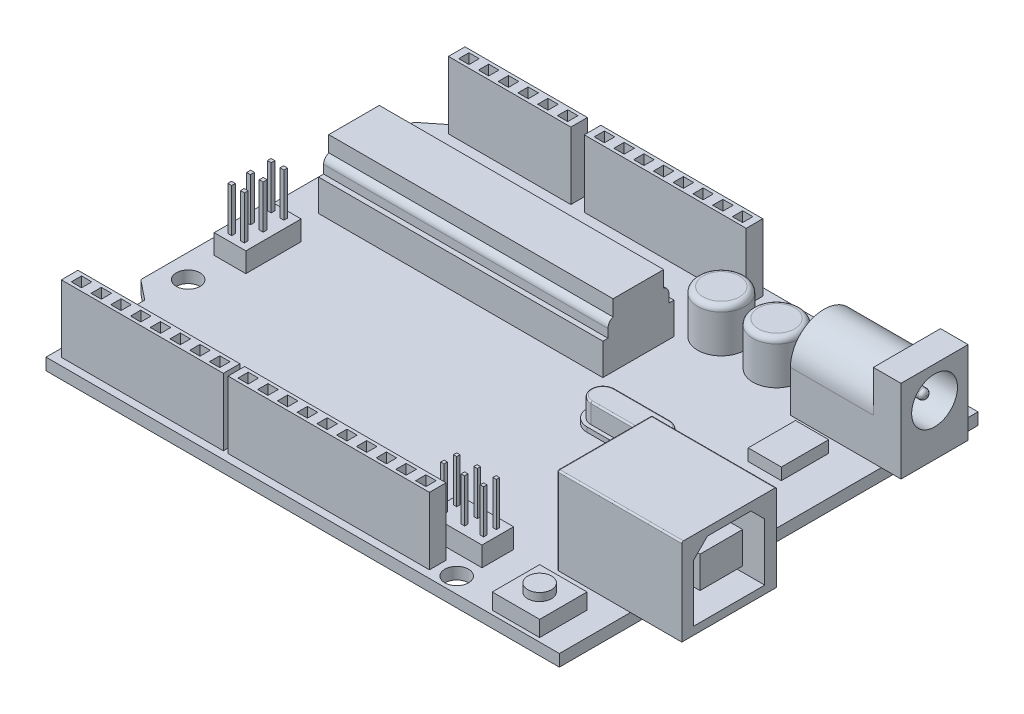
SolidWorks part; units mm, degrees
ref_plane "Front Plane" through (0, 0, 0) normal (0, 0, 1) x (1, 0, 0)
ref_plane "Top Plane" through (0, 0, 0) normal (0, 1, 0) x (1, 0, 0)
ref_plane "Right Plane" through (0, 0, 0) normal (1, 0, 0) x (0, 0, -1)
sketch "Sketch1" plane through (0, 0, 0) normal (0, 1, 0) x (1, 0, 0)
  line L0 (-32.5, -26.5) -> (-32.5, -14)
  line L1 (-32.5, 26.5) -> (32.5, 26.5)
  line L2 (-32.5, 26.5) -> (-32.5, -26.5) construction
  line L3 (-32.5, -26.5) -> (32.5, -26.5)
  line L4 (32.5, 26.5) -> (32.5, -26.5)
  line L5 (-32.5, 26.5) -> (32.5, -26.5) construction
  line L6 (-32.5, -26.5) -> (32.5, 26.5) construction
  line L7 (-32.5, 26.5) -> (-32.5, 24.5)
  line L8 (-32.5, 24.5) -> (-35, 22.5)
  line L9 (-35, 22.5) -> (-35, -12)
  line L10 (-35, -12) -> (-32.5, -14)
  point P0 (0, 0)
  dimension "D1" = 53
  dimension "D2" = 65
  dimension "D3" = 12.5
  dimension "D4" = 2
  dimension "D5" = 2.5
  dimension "D6" = 2
  dimension "D7" = 2
extrude "Boss-Extrude1" add sketch "Sketch1" along normal blind 1.5
sketch "Sketch2" plane through (0, 1.5, 0) normal (0, 1, 0) x (1, 0, 0)
  line L0 (-35, 19) -> (34.4446, 19) construction
  line L1 (-35, 22.5) -> (-35, -12) construction
  line L2 (-37.4466, -9) -> (38.9629, -9) construction
  line L3 (-32.5, -26.5) -> (32.5, -26.5) construction
  line L4 (17.5, -22.2903) -> (17.5, -28.2143) construction
  line L5 (32.5, 26.5) -> (-32.5, 26.5) construction
  line L6 (-32, -11.6472) -> (-32, 23.7964) construction
  line L7 (-36.1413, -24.5) -> (34.4446, -24.5) construction
  line L8 (35.3482, 24.5) -> (-37.4466, 24.5) construction
  line L9 (32.5, -26.5) -> (32.5, 26.5) construction
  line L10 (18.5, 27.8126) -> (18.5, 22.4911) construction
  circle A0 centre (-32, 19) radius 1.5
  circle A1 centre (-32, -9) radius 1.5
  circle A2 centre (18.5, 24.5) radius 1.5
  circle A3 centre (17.5, -24.5) radius 1.5
  dimension "D4" = 3
  dimension "D5" = 3
  dimension "D10" = 3
  dimension "D11" = 3
  dimension "D1" = 17.5
  dimension "D2" = 7.5
  dimension "D3" = 3
  dimension "D6" = 2
  dimension "D7" = 2
  dimension "D8" = 15
  dimension "D9" = 14
extrude "Cut-Extrude1" cut sketch "Sketch2" against normal through all
sketch "Sketch4" plane through (0, 1.5, 0) normal (0, 1, 0) x (1, 0, 0)
  line L0 (32.5, -26.5) -> (32.5, 26.5) construction
  line L1 (23.5, -20) -> (29.5, -20)
  line L2 (23.5, -20) -> (23.5, -26)
  line L3 (23.5, -26) -> (29.5, -26)
  line L4 (29.5, -20) -> (29.5, -26)
  line L5 (23.5, -20) -> (29.5, -26) construction
  line L6 (23.5, -26) -> (29.5, -20) construction
  line L7 (-32.5, -26.5) -> (32.5, -26.5) construction
  point P0 (26.5, -23)
  dimension "D1" = 6
  dimension "D2" = 6
  dimension "D3" = 3
  dimension "D4" = 0.5
extrude "Boss-Extrude3" add sketch "Sketch4" along normal blind 2
sketch "Sketch5" plane through (0, 3.5, 0) normal (0, 1, 0) x (1, 0, 0)
  circle A0 centre (26.5, -23) radius 1.5
  dimension "D1" = 3
extrude "Boss-Extrude4" add sketch "Sketch5" along normal blind 1
sketch "Sketch6" plane through (0, 1.5, 0) normal (0, 1, 0) x (1, 0, 0)
  line L0 (10, 1.5) -> (17, 1.5) construction
  line L1 (10, 3.5) -> (17, 3.5)
  line L2 (10, -0.5) -> (17, -0.5)
  line L3 (8, 1.5) -> (8, 12.5737) construction
  line L4 (19, 1.5) -> (19, 12.5737) construction
  line L5 (32.5, 26.5) -> (-32.5, 26.5) construction
  line L7 (32.5, -26.5) -> (32.5, 26.5) construction
  arc A0 (10, 3.5) -> (10, -0.5) centre (10, 1.5) ccw
  arc A1 (17, -0.5) -> (17, 3.5) centre (17, 1.5) ccw
  point P2 (13.5, 1.5)
  dimension "D2" = 11
  dimension "D1" = 7
  dimension "D3" = 25
  dimension "D4" = 19
extrude "Boss-Extrude5" add sketch "Sketch6" along normal blind 0.6
sketch "Sketch7" plane through (0, 2.1, 0) normal (0, 1, 0) x (1, 0, 0)
  line L0 (10, 1.5) -> (17, 1.5) construction
  line L1 (10, 3) -> (17, 3)
  line L2 (10, 0) -> (17, 0)
  arc A0 (10, 3) -> (10, 0) centre (10, 1.5) ccw
  arc A1 (17, 0) -> (17, 3) centre (17, 1.5) ccw
  point P4 (13.5, 1.5)
extrude "Boss-Extrude6" add sketch "Sketch7" along normal blind 2.5
fillet "Fillet4" radius 0.2 4 edges at (13.5, 4.6, -3) (18.5, 4.6, -1.5) (13.5, 4.6, 0) (8.5, 4.6, -1.5)
sketch "Sketch8" plane through (0, 1.5, 0) normal (0, 1, 0) x (1, 0, 0)
  line L0 (32.5, -26.5) -> (32.5, 26.5) construction
  line L1 (23.2, -5.5) -> (39, -5.5)
  line L2 (23.2, -5.5) -> (23.2, -17.5)
  line L3 (23.2, -17.5) -> (39, -17.5)
  line L4 (39, -5.5) -> (39, -17.5)
  line L5 (23.2, -5.5) -> (39, -17.5) construction
  line L6 (23.2, -17.5) -> (39, -5.5) construction
  line L7 (-32.5, -26.5) -> (32.5, -26.5) construction
  point P0 (31.1, -11.5)
  dimension "D1" = 6.5
  dimension "D2" = 15.8
  dimension "D3" = 12
  dimension "D4" = 9
extrude "Boss-Extrude7" add sketch "Sketch8" along normal blind 11
fillet "Fillet5" radius 0.2 5 edges at (23.2, 7, 5.5) (23.2, 7, 17.5) (23.2, 12.5, 11.5) (31.1, 12.5, 5.5) (31.1, 12.5, 17.5)
sketch "Sketch9" plane through (0, 1.5, 0) normal (0, 1, 0) x (1, 0, 0)
  line L0 (32.5, 26.5) -> (-32.5, 26.5) construction
  line L1 (21, 22.75) -> (35, 22.75)
  line L2 (21, 22.75) -> (21, 14.25)
  line L3 (21, 14.25) -> (35, 14.25)
  line L4 (35, 22.75) -> (35, 14.25)
  line L5 (21, 22.75) -> (35, 14.25) construction
  line L6 (21, 14.25) -> (35, 22.75) construction
  line L7 (32.5, -5.5) -> (32.5, 26.5) construction
  point P0 (28, 18.5)
  dimension "D1" = 8
  dimension "D2" = 14
  dimension "D3" = 2.5
  dimension "D4" = 8.5
extrude "Boss-Extrude8" add sketch "Sketch9" along normal blind 10.5
sketch "Sketch10" plane through (21, 0, 0) normal (-1, 0, 0) x (0, 0, 1)
  line L0 (-22.75, 6.75) -> (-14.25, 6.75) construction
  line L1 (-22.75, 12) -> (-22.75, 1.5) construction
  line L2 (-14.25, 12) -> (-14.25, 1.5) construction
  line L3 (-22.75, 6.75) -> (-24.8341, 6.75)
  line L4 (-24.8341, 6.75) -> (-24.8341, 13.7085)
  line L5 (-24.8341, 13.7085) -> (-12.9417, 13.7085)
  line L6 (-12.9417, 13.7085) -> (-12.9417, 6.75)
  line L7 (-12.9417, 6.75) -> (-14.25, 6.75)
  arc A0 (-22.75, 6.75) -> (-14.25, 6.75) centre (-18.5, 6.75) cw
extrude "Cut-Extrude2" cut sketch "Sketch10" against normal blind 10.5
sketch "Sketch11" plane through (0, 1.5, 0) normal (0, 1, 0) x (1, 0, 0)
  line L0 (-35, 22.5) -> (-35, -12) construction
  line L1 (-31, 15.5) -> (5, 15.5)
  line L2 (-31, 15.5) -> (-31, 6.5)
  line L3 (-31, 6.5) -> (5, 6.5)
  line L4 (5, 15.5) -> (5, 6.5)
  line L5 (-31, 15.5) -> (5, 6.5) construction
  line L6 (-31, 6.5) -> (5, 15.5) construction
  line L7 (32.5, 26.5) -> (-32.5, 26.5) construction
  point P0 (-13, 11)
  dimension "D1" = 36
  dimension "D2" = 9
  dimension "D3" = 4
  dimension "D4" = 11
extrude "Boss-Extrude9" add sketch "Sketch11" along normal blind 4
sketch "Sketch12" plane through (0, 5.5, 0) normal (0, 1, 0) x (1, 0, 0)
  line L0 (-31, 11) -> (5, 11) construction
  line L1 (-31, 15.5) -> (-31, 6.5) construction
  line L2 (5, 6.5) -> (5, 15.5) construction
  line L4 (-31, 14.8545) -> (5, 14.8545)
  line L5 (-31, 14.8545) -> (-31, 7.1455)
  line L6 (-31, 7.1455) -> (5, 7.1455)
  line L7 (5, 14.8545) -> (5, 7.1455)
  line L8 (-31, 14.8545) -> (5, 7.1455) construction
  line L9 (-31, 7.1455) -> (5, 14.8545) construction
  point P6 (-13, 11)
extrude "Boss-Extrude10" add sketch "Sketch12" along normal blind 2
sketch "Sketch13" plane through (0, 7.5, 0) normal (0, 1, 0) x (1, 0, 0)
  line L0 (-31, 11) -> (5, 11) construction
  line L1 (-31, 14.8545) -> (-31, 7.1455) construction
  line L2 (5, 7.1455) -> (5, 14.8545) construction
  line L4 (-31, 14.2021) -> (5, 14.2021)
  line L5 (-31, 14.2021) -> (-31, 7.7979)
  line L6 (-31, 7.7979) -> (5, 7.7979)
  line L7 (5, 14.2021) -> (5, 7.7979)
  line L8 (-31, 14.2021) -> (5, 7.7979) construction
  line L9 (-31, 7.7979) -> (5, 14.2021) construction
  point P6 (-13, 11)
extrude "Boss-Extrude11" add sketch "Sketch13" along normal blind 2
fillet "Fillet6" radius 1 2 edges at (-13, 7.5, -14.8545) (-13, 7.5, -7.1455)
sketch "Sketch15" plane through (0, 1.5, 0) normal (0, 1, 0) x (1, 0, 0)
  line L0 (32.5, -5.5) -> (32.5, 14.25) construction
  line L1 (32.5, 26.5) -> (-32.5, 26.5) construction
  circle A0 centre (15, 18.5) radius 3
  circle A1 centre (8, 18.5) radius 3
  dimension "D1" = 17.5
  dimension "D3" = 6
  dimension "D4" = 6
  dimension "D2" = 8
  dimension "D5" = 7
extrude "Boss-Extrude12" add sketch "Sketch15" along normal blind 5.5
fillet "Fillet7" radius 0.7 2 edges at (15, 7, -15.5) (8, 7, -15.5)
sketch "Sketch16" plane through (0, 1.5, 0) normal (0, 1, 0) x (1, 0, 0)
  line L0 (11.2, -18) -> (18.2, -18)
  line L1 (-33, 2.3) -> (-29, 2.3)
  line L2 (-33, 2.3) -> (-33, -4.7)
  line L3 (-33, -4.7) -> (-29, -4.7)
  line L4 (-29, 2.3) -> (-29, -4.7)
  line L5 (-33, 2.3) -> (-29, -4.7) construction
  line L6 (-33, -4.7) -> (-29, 2.3) construction
  line L7 (11.2, -18) -> (11.2, -22)
  line L8 (11.2, -22) -> (18.2, -22)
  line L9 (18.2, -18) -> (18.2, -22)
  line L10 (11.2, -18) -> (18.2, -22) construction
  line L11 (11.2, -22) -> (18.2, -18) construction
  line L12 (32.5, 26.5) -> (-32.5, 26.5) construction
  line L13 (-35, 22.5) -> (-35, -12) construction
  line L14 (32.5, -26.5) -> (32.5, -17.5) construction
  line L16 (-32.5, -26.5) -> (32.5, -26.5) construction
  point P0 (-31, -1.2)
  point P5 (14.7, -20)
  dimension "D1" = 24.2
  dimension "D2" = 4
  dimension "D3" = 7
  dimension "D4" = 4
  dimension "D5" = 4
  dimension "D6" = 7
  dimension "D7" = 14.3
  dimension "D8" = 4.5
extrude "Boss-Extrude13" add sketch "Sketch16" along normal blind 2.5
sketch "Sketch17" plane through (0, 4, 0) normal (0, 1, 0) x (1, 0, 0)
  line L0 (-31.8, 2.3) -> (-31.8, -4.7) construction
  line L1 (-29, 2.3) -> (-33, 2.3) construction
  line L2 (-33, -4.7) -> (-29, -4.7) construction
  line L3 (-30.2, 2.3) -> (-30.2, -4.7) construction
  line L4 (-29, 2.3) -> (-33, 2.3) construction
  line L5 (-33, -4.7) -> (-29, -4.7) construction
  line L6 (-33, 2.3) -> (-33, -4.7) construction
  line L7 (-29, -4.7) -> (-29, 2.3) construction
  line L8 (-33, 1.3) -> (-29, 1.3) construction
  line L9 (-33, -1.3) -> (-29, -1.3) construction
  line L10 (-33, 2.3) -> (-33, -4.7) construction
  line L11 (-29, -4.7) -> (-29, 2.3) construction
  line L12 (-33, -3.7) -> (-29, -3.7) construction
  line L13 (11.2, -19.2) -> (18.2, -19.2) construction
  line L14 (11.2, -18) -> (11.2, -22) construction
  line L15 (18.2, -22) -> (18.2, -18) construction
  line L16 (11.2, -20.8) -> (18.2, -20.8) construction
  line L17 (18.2, -18) -> (11.2, -18) construction
  line L18 (11.2, -22) -> (18.2, -22) construction
  line L19 (12.2, -18) -> (12.2, -22) construction
  line L20 (11.2, -22) -> (18.2, -22) construction
  line L21 (14.8, -18) -> (14.8, -22) construction
  line L22 (17.2, -18) -> (17.2, -22) construction
  line L23 (18.2, -18) -> (11.2, -18) construction
  line L25 (-32.0421, 1.5304) -> (-31.5579, 1.5304)
  line L26 (-32.0421, 1.5304) -> (-32.0421, 1.0696)
  line L27 (-32.0421, 1.0696) -> (-31.5579, 1.0696)
  line L28 (-31.5579, 1.5304) -> (-31.5579, 1.0696)
  line L29 (-32.0421, 1.5304) -> (-31.5579, 1.0696) construction
  line L30 (-32.0421, 1.0696) -> (-31.5579, 1.5304) construction
  line L31 (-30.4481, 1.5304) -> (-29.9519, 1.5304)
  line L32 (-30.4481, 1.5304) -> (-30.4481, 1.0696)
  line L33 (-30.4481, 1.0696) -> (-29.9519, 1.0696)
  line L34 (-29.9519, 1.5304) -> (-29.9519, 1.0696)
  line L35 (-30.4481, 1.5304) -> (-29.9519, 1.0696) construction
  line L36 (-30.4481, 1.0696) -> (-29.9519, 1.5304) construction
  line L37 (-32.0421, -1.0471) -> (-31.5579, -1.0471)
  line L38 (-32.0421, -1.0471) -> (-32.0421, -1.5529)
  line L39 (-32.0421, -1.5529) -> (-31.5579, -1.5529)
  line L40 (-31.5579, -1.0471) -> (-31.5579, -1.5529)
  line L41 (-32.0421, -1.0471) -> (-31.5579, -1.5529) construction
  line L42 (-32.0421, -1.5529) -> (-31.5579, -1.0471) construction
  line L43 (-30.4481, -1.0471) -> (-29.9519, -1.0471)
  line L44 (-30.4481, -1.0471) -> (-30.4481, -1.5529)
  line L45 (-30.4481, -1.5529) -> (-29.9519, -1.5529)
  line L46 (-29.9519, -1.0471) -> (-29.9519, -1.5529)
  line L47 (-30.4481, -1.0471) -> (-29.9519, -1.5529) construction
  line L48 (-30.4481, -1.5529) -> (-29.9519, -1.0471) construction
  line L49 (-32.0421, -3.4686) -> (-31.5579, -3.4686)
  line L50 (-32.0421, -3.4686) -> (-32.0421, -3.9314)
  line L51 (-32.0421, -3.9314) -> (-31.5579, -3.9314)
  line L52 (-31.5579, -3.4686) -> (-31.5579, -3.9314)
  line L53 (-32.0421, -3.4686) -> (-31.5579, -3.9314) construction
  line L54 (-32.0421, -3.9314) -> (-31.5579, -3.4686) construction
  line L55 (-30.4481, -3.4686) -> (-29.9519, -3.4686)
  line L56 (-30.4481, -3.4686) -> (-30.4481, -3.9314)
  line L57 (-30.4481, -3.9314) -> (-29.9519, -3.9314)
  line L58 (-29.9519, -3.4686) -> (-29.9519, -3.9314)
  line L59 (-30.4481, -3.4686) -> (-29.9519, -3.9314) construction
  line L60 (-30.4481, -3.9314) -> (-29.9519, -3.4686) construction
  line L61 (11.9899, -18.9946) -> (12.4101, -18.9946)
  line L62 (11.9899, -18.9946) -> (11.9899, -19.4054)
  line L63 (11.9899, -19.4054) -> (12.4101, -19.4054)
  line L64 (12.4101, -18.9946) -> (12.4101, -19.4054)
  line L65 (11.9899, -18.9946) -> (12.4101, -19.4054) construction
  line L66 (11.9899, -19.4054) -> (12.4101, -18.9946) construction
  line L67 (14.5761, -18.9946) -> (15.0239, -18.9946)
  line L68 (14.5761, -18.9946) -> (14.5761, -19.4054)
  line L69 (14.5761, -19.4054) -> (15.0239, -19.4054)
  line L70 (15.0239, -18.9946) -> (15.0239, -19.4054)
  line L71 (14.5761, -18.9946) -> (15.0239, -19.4054) construction
  line L72 (14.5761, -19.4054) -> (15.0239, -18.9946) construction
  line L73 (16.9801, -18.9946) -> (17.4199, -18.9946)
  line L74 (16.9801, -18.9946) -> (16.9801, -19.4054)
  line L75 (16.9801, -19.4054) -> (17.4199, -19.4054)
  line L76 (17.4199, -18.9946) -> (17.4199, -19.4054)
  line L77 (16.9801, -18.9946) -> (17.4199, -19.4054) construction
  line L78 (16.9801, -19.4054) -> (17.4199, -18.9946) construction
  line L79 (11.9899, -20.5827) -> (12.4101, -20.5827)
  line L80 (11.9899, -20.5827) -> (11.9899, -21.0173)
  line L81 (11.9899, -21.0173) -> (12.4101, -21.0173)
  line L82 (12.4101, -20.5827) -> (12.4101, -21.0173)
  line L83 (11.9899, -20.5827) -> (12.4101, -21.0173) construction
  line L84 (11.9899, -21.0173) -> (12.4101, -20.5827) construction
  line L85 (14.5761, -20.5827) -> (15.0239, -20.5827)
  line L86 (14.5761, -20.5827) -> (14.5761, -21.0173)
  line L87 (14.5761, -21.0173) -> (15.0239, -21.0173)
  line L88 (15.0239, -20.5827) -> (15.0239, -21.0173)
  line L89 (14.5761, -20.5827) -> (15.0239, -21.0173) construction
  line L90 (14.5761, -21.0173) -> (15.0239, -20.5827) construction
  line L91 (16.9801, -20.5827) -> (17.4199, -20.5827)
  line L92 (16.9801, -20.5827) -> (16.9801, -21.0173)
  line L93 (16.9801, -21.0173) -> (17.4199, -21.0173)
  line L94 (17.4199, -20.5827) -> (17.4199, -21.0173)
  line L95 (16.9801, -20.5827) -> (17.4199, -21.0173) construction
  line L96 (16.9801, -21.0173) -> (17.4199, -20.5827) construction
  point P48 (-31.8, 1.3)
  point P53 (-30.2, 1.3)
  point P58 (-31.8, -1.3)
  point P63 (-30.2, -1.3)
  point P68 (-31.8, -3.7)
  point P73 (-30.2, -3.7)
  point P78 (12.2, -19.2)
  point P83 (14.8, -19.2)
  point P88 (17.2, -19.2)
  point P93 (12.2, -20.8)
  point P98 (14.8, -20.8)
  point P103 (17.2, -20.8)
  dimension "D1" = 1.2
  dimension "D2" = 1
  dimension "D3" = 1.2
  dimension "D4" = 1
  dimension "D5" = 2.6
  dimension "D6" = 1.2
  dimension "D7" = 1.2
  dimension "D8" = 1
  dimension "D9" = 1
  dimension "D10" = 2.6
extrude "Boss-Extrude14" add sketch "Sketch17" along normal blind 5.5
sketch "Sketch18" plane through (0, 1.5, 0) normal (0, 1, 0) x (1, 0, 0)
  line L0 (32.5, 26.5) -> (-32.5, 26.5) construction
  line L1 (-31.5, -25.55) -> (-11, -25.55)
  line L2 (-31.5, -25.55) -> (-31.5, -23.45)
  line L3 (-31.5, -23.45) -> (-11, -23.45)
  line L4 (-11, -25.55) -> (-11, -23.45)
  line L5 (-31.5, -25.55) -> (-11, -23.45) construction
  line L6 (-31.5, -23.45) -> (-11, -25.55) construction
  line L7 (-10.4, -25.55) -> (15.1, -25.55)
  line L8 (-10.4, -25.55) -> (-10.4, -23.45)
  line L9 (-10.4, -23.45) -> (15.1, -23.45)
  line L10 (15.1, -25.55) -> (15.1, -23.45)
  line L11 (-10.4, -25.55) -> (15.1, -23.45) construction
  line L12 (-10.4, -23.45) -> (15.1, -25.55) construction
  line L13 (-31.5, 25.55) -> (-16, 25.55)
  line L14 (-31.5, 25.55) -> (-31.5, 23.45)
  line L15 (-31.5, 23.45) -> (-16, 23.45)
  line L16 (-16, 25.55) -> (-16, 23.45)
  line L17 (-31.5, 25.55) -> (-16, 23.45) construction
  line L18 (-31.5, 23.45) -> (-16, 25.55) construction
  line L19 (-14.3, 25.55) -> (6.2, 25.55)
  line L20 (-14.3, 25.55) -> (-14.3, 23.45)
  line L21 (-14.3, 23.45) -> (6.2, 23.45)
  line L22 (6.2, 25.55) -> (6.2, 23.45)
  line L23 (-14.3, 25.55) -> (6.2, 23.45) construction
  line L24 (-14.3, 23.45) -> (6.2, 25.55) construction
  line L25 (-32.5, -26.5) -> (32.5, -26.5) construction
  line L26 (-32.5, -14) -> (-32.5, -26.5) construction
  point P4 (-21.25, -24.5)
  point P9 (2.35, -24.5)
  point P14 (-23.75, 24.5)
  point P19 (-4.05, 24.5)
  dimension "D1" = 2.1
  dimension "D2" = 2.1
  dimension "D3" = 2.1
  dimension "D4" = 2.1
  dimension "D5" = 15.5
  dimension "D6" = 20.5
  dimension "D7" = 20.5
  dimension "D8" = 25.5
  dimension "D9" = 2
  dimension "D10" = 2
  dimension "D11" = 2
  dimension "D12" = 2
  dimension "D13" = 1
  dimension "D14" = 0.6
  dimension "D15" = 1
  dimension "D16" = 1.7
extrude "Boss-Extrude15" add sketch "Sketch18" along normal blind 8.5
sketch "Sketch19" plane through (0, 10, 0) normal (0, 1, 0) x (1, 0, 0)
  line L0 (-31.5, 24.5) -> (6.2, 24.5) construction
  line L1 (-31.5, 25.55) -> (-31.5, 23.45) construction
  line L2 (6.2, 23.45) -> (6.2, 25.55) construction
  line L3 (-29.95, 25.55) -> (-29.95, 23.45) construction
  line L4 (-16, 25.55) -> (-31.5, 25.55) construction
  line L5 (-31.5, 23.45) -> (-16, 23.45) construction
  line L6 (-27.45, 25.55) -> (-27.45, 23.45) construction
  line L7 (-31.5, 23.45) -> (-16, 23.45) construction
  line L8 (-24.95, 25.55) -> (-24.95, 23.45) construction
  line L9 (-22.45, 25.55) -> (-22.45, 23.45) construction
  line L10 (-16, 25.55) -> (-31.5, 25.55) construction
  line L11 (-19.95, 25.55) -> (-19.95, 23.45) construction
  line L12 (-17.45, 25.55) -> (-17.45, 23.45) construction
  line L13 (-12.8, 25.55) -> (-12.8, 23.45) construction
  line L14 (6.2, 25.55) -> (-14.3, 25.55) construction
  line L15 (-14.3, 23.45) -> (6.2, 23.45) construction
  line L16 (-10.3, 25.55) -> (-10.3, 23.45) construction
  line L17 (-14.3, 23.45) -> (6.2, 23.45) construction
  line L18 (-7.8, 25.55) -> (-7.8, 23.45) construction
  line L19 (-5.3, 25.55) -> (-5.3, 23.45) construction
  line L20 (-2.8, 25.55) -> (-2.8, 23.45) construction
  line L21 (-0.3, 25.55) -> (-0.3, 23.45) construction
  line L22 (6.2, 25.55) -> (-14.3, 25.55) construction
  line L23 (2.2, 25.55) -> (2.2, 23.45) construction
  line L24 (4.7, 25.55) -> (4.7, 23.45) construction
  line L25 (-31.5, -24.5) -> (15.1, -24.5) construction
  line L26 (-31.5, -23.45) -> (-31.5, -25.55) construction
  line L27 (15.1, -25.55) -> (15.1, -23.45) construction
  line L28 (-30, -23.45) -> (-30, -25.55) construction
  line L29 (-11, -23.45) -> (-31.5, -23.45) construction
  line L30 (-31.5, -25.55) -> (-11, -25.55) construction
  line L31 (-27.5, -23.45) -> (-27.5, -25.55) construction
  line L32 (-25, -23.45) -> (-25, -25.55) construction
  line L33 (-11, -23.45) -> (-31.5, -23.45) construction
  line L34 (-31.5, -25.55) -> (-11, -25.55) construction
  line L35 (-22.5, -23.45) -> (-22.5, -25.55) construction
  line L36 (-20, -23.45) -> (-20, -25.55) construction
  line L37 (-17.5, -23.45) -> (-17.5, -25.55) construction
  line L38 (-15, -23.45) -> (-15, -25.55) construction
  line L39 (-12.5, -23.45) -> (-12.5, -25.55) construction
  line L40 (-8.9, -23.45) -> (-8.9, -25.55) construction
  line L41 (15.1, -23.45) -> (-10.4, -23.45) construction
  line L42 (-10.4, -25.55) -> (15.1, -25.55) construction
  line L43 (-6.4, -23.45) -> (-6.4, -25.55) construction
  line L44 (15.1, -23.45) -> (-10.4, -23.45) construction
  line L45 (-3.9, -23.45) -> (-3.9, -25.55) construction
  line L46 (-1.4, -23.45) -> (-1.4, -25.55) construction
  line L47 (1.1, -23.45) -> (1.1, -25.55) construction
  line L48 (3.6, -23.45) -> (3.6, -25.55) construction
  line L49 (6.1, -23.45) -> (6.1, -25.55) construction
  line L50 (8.6, -23.45) -> (8.6, -25.55) construction
  line L51 (11.1, -23.45) -> (11.1, -25.55) construction
  line L52 (13.6, -23.45) -> (13.6, -25.55) construction
  line L53 (-7.05, -23.85) -> (-5.75, -23.85)
  line L54 (-31.5, 25.55) -> (-31.5, 23.45) construction
  line L55 (-14.3, 25.55) -> (-14.3, 23.45) construction
  line L56 (-10.4, -23.45) -> (-10.4, -25.55) construction
  line L57 (-7.05, -23.85) -> (-7.05, -25.15)
  line L58 (-7.05, -25.15) -> (-5.75, -25.15)
  line L59 (-9.55, -23.85) -> (-8.25, -23.85)
  line L60 (-9.55, -23.85) -> (-9.55, -25.15)
  line L61 (-9.55, -25.15) -> (-8.25, -25.15)
  line L62 (-8.25, -23.85) -> (-8.25, -25.15)
  line L63 (-9.55, -23.85) -> (-8.25, -25.15) construction
  line L64 (-9.55, -25.15) -> (-8.25, -23.85) construction
  line L65 (-5.75, -23.85) -> (-5.75, -25.15)
  line L66 (-29, -24.5) -> (17.6, -24.5) construction
  line L67 (-6.4, -23.45) -> (-6.4, -25.55) construction
  line L68 (-7.05, -23.85) -> (-5.75, -25.15) construction
  line L69 (-7.05, -25.15) -> (-5.75, -23.85) construction
  line L70 (-4.55, -23.85) -> (-3.25, -23.85)
  line L71 (-4.55, -23.85) -> (-4.55, -25.15)
  line L72 (-4.55, -25.15) -> (-3.25, -25.15)
  line L73 (-3.25, -23.85) -> (-3.25, -25.15)
  line L74 (-26.5, -24.5) -> (20.1, -24.5) construction
  line L75 (-3.9, -23.45) -> (-3.9, -25.55) construction
  line L76 (-4.55, -23.85) -> (-3.25, -25.15) construction
  line L77 (-4.55, -25.15) -> (-3.25, -23.85) construction
  line L78 (-2.05, -23.85) -> (-0.75, -23.85)
  line L79 (-2.05, -23.85) -> (-2.05, -25.15)
  line L80 (-2.05, -25.15) -> (-0.75, -25.15)
  line L81 (-0.75, -23.85) -> (-0.75, -25.15)
  line L82 (-24, -24.5) -> (22.6, -24.5) construction
  line L83 (-1.4, -23.45) -> (-1.4, -25.55) construction
  line L84 (-2.05, -23.85) -> (-0.75, -25.15) construction
  line L85 (-2.05, -25.15) -> (-0.75, -23.85) construction
  line L86 (0.45, -23.85) -> (1.75, -23.85)
  line L87 (0.45, -23.85) -> (0.45, -25.15)
  line L88 (0.45, -25.15) -> (1.75, -25.15)
  line L89 (1.75, -23.85) -> (1.75, -25.15)
  line L90 (-21.5, -24.5) -> (25.1, -24.5) construction
  line L91 (1.1, -23.45) -> (1.1, -25.55) construction
  line L92 (0.45, -23.85) -> (1.75, -25.15) construction
  line L93 (0.45, -25.15) -> (1.75, -23.85) construction
  line L94 (2.95, -23.85) -> (4.25, -23.85)
  line L95 (2.95, -23.85) -> (2.95, -25.15)
  line L96 (2.95, -25.15) -> (4.25, -25.15)
  line L97 (4.25, -23.85) -> (4.25, -25.15)
  line L98 (-19, -24.5) -> (27.6, -24.5) construction
  line L99 (3.6, -23.45) -> (3.6, -25.55) construction
  line L100 (2.95, -23.85) -> (4.25, -25.15) construction
  line L101 (2.95, -25.15) -> (4.25, -23.85) construction
  line L102 (5.45, -23.85) -> (6.75, -23.85)
  line L103 (5.45, -23.85) -> (5.45, -25.15)
  line L104 (5.45, -25.15) -> (6.75, -25.15)
  line L105 (6.75, -23.85) -> (6.75, -25.15)
  line L106 (-16.5, -24.5) -> (30.1, -24.5) construction
  line L107 (6.1, -23.45) -> (6.1, -25.55) construction
  line L108 (5.45, -23.85) -> (6.75, -25.15) construction
  line L109 (5.45, -25.15) -> (6.75, -23.85) construction
  line L110 (7.95, -23.85) -> (9.25, -23.85)
  line L111 (7.95, -23.85) -> (7.95, -25.15)
  line L112 (7.95, -25.15) -> (9.25, -25.15)
  line L113 (9.25, -23.85) -> (9.25, -25.15)
  line L114 (-14, -24.5) -> (32.6, -24.5) construction
  line L115 (8.6, -23.45) -> (8.6, -25.55) construction
  line L116 (7.95, -23.85) -> (9.25, -25.15) construction
  line L117 (7.95, -25.15) -> (9.25, -23.85) construction
  line L118 (10.45, -23.85) -> (11.75, -23.85)
  line L119 (10.45, -23.85) -> (10.45, -25.15)
  line L120 (10.45, -25.15) -> (11.75, -25.15)
  line L121 (11.75, -23.85) -> (11.75, -25.15)
  line L122 (-11.5, -24.5) -> (35.1, -24.5) construction
  line L123 (11.1, -23.45) -> (11.1, -25.55) construction
  line L124 (10.45, -23.85) -> (11.75, -25.15) construction
  line L125 (10.45, -25.15) -> (11.75, -23.85) construction
  line L126 (12.95, -23.85) -> (14.25, -23.85)
  line L127 (12.95, -23.85) -> (12.95, -25.15)
  line L128 (12.95, -25.15) -> (14.25, -25.15)
  line L129 (14.25, -23.85) -> (14.25, -25.15)
  line L130 (-9, -24.5) -> (37.6, -24.5) construction
  line L131 (13.6, -23.45) -> (13.6, -25.55) construction
  line L132 (12.95, -23.85) -> (14.25, -25.15) construction
  line L133 (12.95, -25.15) -> (14.25, -23.85) construction
  line L134 (-28.15, -25.15) -> (-26.85, -25.15)
  line L135 (-30.65, -25.15) -> (-29.35, -25.15)
  line L136 (-30.65, -25.15) -> (-30.65, -23.85)
  line L137 (-30.65, -23.85) -> (-29.35, -23.85)
  line L138 (-29.35, -25.15) -> (-29.35, -23.85)
  line L139 (-30.65, -25.15) -> (-29.35, -23.85) construction
  line L140 (-30.65, -23.85) -> (-29.35, -25.15) construction
  line L141 (-28.15, -25.15) -> (-28.15, -23.85)
  line L142 (-28.15, -23.85) -> (-26.85, -23.85)
  line L143 (-26.85, -25.15) -> (-26.85, -23.85)
  line L144 (-27.5, -23.45) -> (-27.5, -25.55) construction
  line L145 (-26.5, -24.5) -> (20.1, -24.5) construction
  line L146 (-28.15, -25.15) -> (-26.85, -23.85) construction
  line L147 (-28.15, -23.85) -> (-26.85, -25.15) construction
  line L148 (-25.65, -25.15) -> (-24.35, -25.15)
  line L149 (-25.65, -25.15) -> (-25.65, -23.85)
  line L150 (-25.65, -23.85) -> (-24.35, -23.85)
  line L151 (-24.35, -25.15) -> (-24.35, -23.85)
  line L152 (-25, -23.45) -> (-25, -25.55) construction
  line L153 (-24, -24.5) -> (22.6, -24.5) construction
  line L154 (-25.65, -25.15) -> (-24.35, -23.85) construction
  line L155 (-25.65, -23.85) -> (-24.35, -25.15) construction
  line L156 (-23.15, -25.15) -> (-21.85, -25.15)
  line L157 (-23.15, -25.15) -> (-23.15, -23.85)
  line L158 (-23.15, -23.85) -> (-21.85, -23.85)
  line L159 (-21.85, -25.15) -> (-21.85, -23.85)
  line L160 (-22.5, -23.45) -> (-22.5, -25.55) construction
  line L161 (-21.5, -24.5) -> (25.1, -24.5) construction
  line L162 (-23.15, -25.15) -> (-21.85, -23.85) construction
  line L163 (-23.15, -23.85) -> (-21.85, -25.15) construction
  line L164 (-20.65, -25.15) -> (-19.35, -25.15)
  line L165 (-20.65, -25.15) -> (-20.65, -23.85)
  line L166 (-20.65, -23.85) -> (-19.35, -23.85)
  line L167 (-19.35, -25.15) -> (-19.35, -23.85)
  line L168 (-20, -23.45) -> (-20, -25.55) construction
  line L169 (-19, -24.5) -> (27.6, -24.5) construction
  line L170 (-20.65, -25.15) -> (-19.35, -23.85) construction
  line L171 (-20.65, -23.85) -> (-19.35, -25.15) construction
  line L172 (-18.15, -25.15) -> (-16.85, -25.15)
  line L173 (-18.15, -25.15) -> (-18.15, -23.85)
  line L174 (-18.15, -23.85) -> (-16.85, -23.85)
  line L175 (-16.85, -25.15) -> (-16.85, -23.85)
  line L176 (-17.5, -23.45) -> (-17.5, -25.55) construction
  line L177 (-16.5, -24.5) -> (30.1, -24.5) construction
  line L178 (-18.15, -25.15) -> (-16.85, -23.85) construction
  line L179 (-18.15, -23.85) -> (-16.85, -25.15) construction
  line L180 (-15.65, -25.15) -> (-14.35, -25.15)
  line L181 (-15.65, -25.15) -> (-15.65, -23.85)
  line L182 (-15.65, -23.85) -> (-14.35, -23.85)
  line L183 (-14.35, -25.15) -> (-14.35, -23.85)
  line L184 (-15, -23.45) -> (-15, -25.55) construction
  line L185 (-14, -24.5) -> (32.6, -24.5) construction
  line L186 (-15.65, -25.15) -> (-14.35, -23.85) construction
  line L187 (-15.65, -23.85) -> (-14.35, -25.15) construction
  line L188 (-13.15, -25.15) -> (-11.85, -25.15)
  line L189 (-13.15, -25.15) -> (-13.15, -23.85)
  line L190 (-13.15, -23.85) -> (-11.85, -23.85)
  line L191 (-11.85, -25.15) -> (-11.85, -23.85)
  line L192 (-12.5, -23.45) -> (-12.5, -25.55) construction
  line L193 (-11.5, -24.5) -> (35.1, -24.5) construction
  line L194 (-13.15, -25.15) -> (-11.85, -23.85) construction
  line L195 (-13.15, -23.85) -> (-11.85, -25.15) construction
  line L196 (-28.1, 25.15) -> (-26.8, 25.15)
  line L197 (-30.6, 25.15) -> (-29.3, 25.15)
  line L198 (-30.6, 25.15) -> (-30.6, 23.85)
  line L199 (-30.6, 23.85) -> (-29.3, 23.85)
  line L200 (-29.3, 25.15) -> (-29.3, 23.85)
  line L201 (-30.6, 25.15) -> (-29.3, 23.85) construction
  line L202 (-30.6, 23.85) -> (-29.3, 25.15) construction
  line L203 (-28.1, 25.15) -> (-28.1, 23.85)
  line L204 (-28.1, 23.85) -> (-26.8, 23.85)
  line L205 (-26.8, 25.15) -> (-26.8, 23.85)
  line L206 (-28.1, 25.15) -> (-26.8, 23.85) construction
  line L207 (-28.1, 23.85) -> (-26.8, 25.15) construction
  line L208 (-25.6, 25.15) -> (-24.3, 25.15)
  line L209 (-25.6, 25.15) -> (-25.6, 23.85)
  line L210 (-25.6, 23.85) -> (-24.3, 23.85)
  line L211 (-24.3, 25.15) -> (-24.3, 23.85)
  line L212 (-25.6, 25.15) -> (-24.3, 23.85) construction
  line L213 (-25.6, 23.85) -> (-24.3, 25.15) construction
  line L214 (-23.1, 25.15) -> (-21.8, 25.15)
  line L215 (-23.1, 25.15) -> (-23.1, 23.85)
  line L216 (-23.1, 23.85) -> (-21.8, 23.85)
  line L217 (-21.8, 25.15) -> (-21.8, 23.85)
  line L218 (-23.1, 25.15) -> (-21.8, 23.85) construction
  line L219 (-23.1, 23.85) -> (-21.8, 25.15) construction
  line L220 (-20.6, 25.15) -> (-19.3, 25.15)
  line L221 (-20.6, 25.15) -> (-20.6, 23.85)
  line L222 (-20.6, 23.85) -> (-19.3, 23.85)
  line L223 (-19.3, 25.15) -> (-19.3, 23.85)
  line L224 (-20.6, 25.15) -> (-19.3, 23.85) construction
  line L225 (-20.6, 23.85) -> (-19.3, 25.15) construction
  line L226 (-18.1, 25.15) -> (-16.8, 25.15)
  line L227 (-18.1, 25.15) -> (-18.1, 23.85)
  line L228 (-18.1, 23.85) -> (-16.8, 23.85)
  line L229 (-16.8, 25.15) -> (-16.8, 23.85)
  line L230 (-18.1, 25.15) -> (-16.8, 23.85) construction
  line L231 (-18.1, 23.85) -> (-16.8, 25.15) construction
  line L232 (-10.95, 25.15) -> (-9.65, 25.15)
  line L233 (-13.45, 25.15) -> (-12.15, 25.15)
  line L234 (-13.45, 25.15) -> (-13.45, 23.85)
  line L235 (-13.45, 23.85) -> (-12.15, 23.85)
  line L236 (-12.15, 25.15) -> (-12.15, 23.85)
  line L237 (-13.45, 25.15) -> (-12.15, 23.85) construction
  line L238 (-13.45, 23.85) -> (-12.15, 25.15) construction
  line L239 (-10.95, 25.15) -> (-10.95, 23.85)
  line L240 (-10.95, 23.85) -> (-9.65, 23.85)
  line L241 (-9.65, 25.15) -> (-9.65, 23.85)
  line L242 (-10.3, 25.55) -> (-10.3, 23.45) construction
  line L243 (-10.95, 25.15) -> (-9.65, 23.85) construction
  line L244 (-10.95, 23.85) -> (-9.65, 25.15) construction
  line L245 (-8.45, 25.15) -> (-7.15, 25.15)
  line L246 (-8.45, 25.15) -> (-8.45, 23.85)
  line L247 (-8.45, 23.85) -> (-7.15, 23.85)
  line L248 (-7.15, 25.15) -> (-7.15, 23.85)
  line L249 (-7.8, 25.55) -> (-7.8, 23.45) construction
  line L250 (-8.45, 25.15) -> (-7.15, 23.85) construction
  line L251 (-8.45, 23.85) -> (-7.15, 25.15) construction
  line L252 (-5.95, 25.15) -> (-4.65, 25.15)
  line L253 (-5.95, 25.15) -> (-5.95, 23.85)
  line L254 (-5.95, 23.85) -> (-4.65, 23.85)
  line L255 (-4.65, 25.15) -> (-4.65, 23.85)
  line L256 (-5.3, 25.55) -> (-5.3, 23.45) construction
  line L257 (-5.95, 25.15) -> (-4.65, 23.85) construction
  line L258 (-5.95, 23.85) -> (-4.65, 25.15) construction
  line L259 (-3.45, 25.15) -> (-2.15, 25.15)
  line L260 (-3.45, 25.15) -> (-3.45, 23.85)
  line L261 (-3.45, 23.85) -> (-2.15, 23.85)
  line L262 (-2.15, 25.15) -> (-2.15, 23.85)
  line L263 (-2.8, 25.55) -> (-2.8, 23.45) construction
  line L264 (-3.45, 25.15) -> (-2.15, 23.85) construction
  line L265 (-3.45, 23.85) -> (-2.15, 25.15) construction
  line L266 (-0.95, 25.15) -> (0.35, 25.15)
  line L267 (-0.95, 25.15) -> (-0.95, 23.85)
  line L268 (-0.95, 23.85) -> (0.35, 23.85)
  line L269 (0.35, 25.15) -> (0.35, 23.85)
  line L270 (-0.3, 25.55) -> (-0.3, 23.45) construction
  line L271 (-0.95, 25.15) -> (0.35, 23.85) construction
  line L272 (-0.95, 23.85) -> (0.35, 25.15) construction
  line L273 (1.55, 25.15) -> (2.85, 25.15)
  line L274 (1.55, 25.15) -> (1.55, 23.85)
  line L275 (1.55, 23.85) -> (2.85, 23.85)
  line L276 (2.85, 25.15) -> (2.85, 23.85)
  line L277 (2.2, 25.55) -> (2.2, 23.45) construction
  line L278 (1.55, 25.15) -> (2.85, 23.85) construction
  line L279 (1.55, 23.85) -> (2.85, 25.15) construction
  line L280 (4.05, 25.15) -> (5.35, 25.15)
  line L281 (4.05, 25.15) -> (4.05, 23.85)
  line L282 (4.05, 23.85) -> (5.35, 23.85)
  line L283 (5.35, 25.15) -> (5.35, 23.85)
  line L284 (4.7, 25.55) -> (4.7, 23.45) construction
  line L285 (4.05, 25.15) -> (5.35, 23.85) construction
  line L286 (4.05, 23.85) -> (5.35, 25.15) construction
  point P112 (-8.9, -24.5)
  point P117 (-30, -24.5)
  point P122 (-6.4, -24.5)
  point P131 (-3.9, -24.5)
  point P140 (-1.4, -24.5)
  point P149 (1.1, -24.5)
  point P158 (3.6, -24.5)
  point P167 (6.1, -24.5)
  point P176 (8.6, -24.5)
  point P185 (11.1, -24.5)
  point P194 (13.6, -24.5)
  point P203 (-29.95, 24.5)
  point P206 (-27.5, -24.5)
  point P215 (-25, -24.5)
  point P224 (-22.5, -24.5)
  point P233 (-20, -24.5)
  point P242 (-17.5, -24.5)
  point P251 (-15, -24.5)
  point P260 (-12.5, -24.5)
  point P271 (-12.8, 24.5)
  point P272 (-27.45, 24.5)
  point P277 (-24.95, 24.5)
  point P282 (-22.45, 24.5)
  point P287 (-19.95, 24.5)
  point P292 (-17.45, 24.5)
  point P304 (-10.3, 24.5)
  point P311 (-7.8, 24.5)
  point P318 (-5.3, 24.5)
  point P325 (-2.8, 24.5)
  point P332 (-0.3, 24.5)
  point P339 (2.2, 24.5)
  point P346 (4.7, 24.5)
  dimension "D1" = 2.5
  dimension "D2" = 2.5
  dimension "D3" = 2.5
  dimension "D4" = 2.5
  dimension "D5" = 2.5
  dimension "D6" = 1.55
  dimension "D7" = 1.5
  dimension "D8" = 2.5
  dimension "D9" = 2.5
  dimension "D10" = 2.5
  dimension "D11" = 2.5
  dimension "D12" = 2.5
  dimension "D13" = 2.5
  dimension "D14" = 2.5
  dimension "D15" = 1.5
  dimension "D16" = 2.5
  dimension "D17" = 2.5
  dimension "D18" = 2.5
  dimension "D19" = 2.5
  dimension "D20" = 2.5
  dimension "D21" = 2.5
  dimension "D22" = 2.5
  dimension "D23" = 1.5
  dimension "D24" = 2.5
  dimension "D25" = 2.5
  dimension "D26" = 2.5
  dimension "D27" = 2.5
  dimension "D28" = 2.5
  dimension "D29" = 2.5
  dimension "D30" = 2.5
  dimension "D31" = 2.5
  dimension "D32" = 2.5
  dimension "D33" = 1.3
  dimension "D34" = 1.3
  dimension "D36" = 1.3
  dimension "D37" = 1.3
  dimension "D39" = 1.3
  dimension "D40" = 1.3
  dimension "D42" = 8
  dimension "D35" = 10
  dimension "D38" = 8
  dimension "D41" = 6
extrude "Cut-Extrude4" cut sketch "Sketch19" against normal blind 6
sketch "Sketch20" plane through (35, 0, 0) normal (1, 0, 0) x (0, 0, -1)
  line L0 (18.5, 1.5) -> (18.5, 8) construction
  line L1 (14.25, 1.5) -> (22.75, 1.5) construction
  circle A0 centre (18.5, 8) radius 2.9
  dimension "D2" = 5.8
  dimension "D1" = 6.5
extrude "Cut-Extrude5" cut sketch "Sketch20" against normal blind 12
sketch "Sketch21" plane through (23, 0, 0) normal (1, 0, 0) x (0, 0, -1)
  circle A0 centre (18.5, 8) radius 0.6
  dimension "D1" = 1.2
extrude "Boss-Extrude16" add sketch "Sketch21" along normal blind 11
fillet "Fillet8" radius 0.5 1 edges at (34, 8, -19.1)
sketch "Sketch22" plane through (39, 0, 0) normal (1, 0, 0) x (0, 0, -1)
  line L0 (-17.5, 12.3) -> (-17.5, 1.5) construction
  line L1 (-16, 2.5) -> (-7, 2.5)
  line L2 (-16, 2.5) -> (-16, 9.75)
  line L3 (-16, 11.5) -> (-7, 11.5) construction
  line L4 (-7, 2.5) -> (-7, 9.75)
  line L5 (-16, 2.5) -> (-7, 11.5) construction
  line L6 (-16, 11.5) -> (-7, 2.5) construction
  line L7 (-17.5, 1.5) -> (-5.5, 1.5) construction
  line L8 (-11.5, 2.5) -> (-11.5, 11.5) construction
  line L9 (-8.75, 13.4132) -> (-8.75, 9.4418) construction
  line L10 (-14.25, 15.5935) -> (-14.25, 9.75) construction
  line L11 (-14.25, 11.5) -> (-16, 9.75)
  line L12 (-8.75, 11.5) -> (-7, 9.75)
  line L13 (-14.25, 11.5) -> (-8.75, 11.5)
  point P0 (-11.5, 7)
  dimension "D1" = 9
  dimension "D2" = 9
  dimension "D3" = 1.5
  dimension "D4" = 1
  dimension "D5" = 2.75
  dimension "D6" = 2.75
extrude "Cut-Extrude6" cut sketch "Sketch22" against normal blind 12
sketch "Sketch23" plane through (27, 0, 0) normal (1, 0, 0) x (0, 0, -1)
  line L0 (-11.5, 11.5) -> (-11.5, 2.5) construction
  line L1 (-8.75, 11.5) -> (-14.25, 11.5) construction
  line L2 (-16, 2.5) -> (-7, 2.5) construction
  line L4 (-14.2, 9) -> (-8.8, 9)
  line L5 (-14.2, 9) -> (-14.2, 5)
  line L6 (-14.2, 5) -> (-8.8, 5)
  line L7 (-8.8, 9) -> (-8.8, 5)
  line L8 (-14.2, 9) -> (-8.8, 5) construction
  line L9 (-14.2, 5) -> (-8.8, 9) construction
  point P6 (-11.5, 7)
  dimension "D1" = 5.4
  dimension "D2" = 4
extrude "Boss-Extrude17" add sketch "Sketch23" along normal blind 11
sketch "Sketch24" plane through (0, 1.5, 0) normal (0, 1, 0) x (1, 0, 0)
  line L0 (32.5, 26.5) -> (-32.5, 26.5) construction
  line L1 (23.4, 12.5) -> (27.6, 12.5)
  line L2 (23.4, 12.5) -> (23.4, 6.5)
  line L3 (23.4, 6.5) -> (27.6, 6.5)
  line L4 (27.6, 12.5) -> (27.6, 6.5)
  line L5 (23.4, 12.5) -> (27.6, 6.5) construction
  line L6 (23.4, 6.5) -> (27.6, 12.5) construction
  line L7 (32.5, -5.5) -> (32.5, 14.25) construction
  point P0 (25.5, 9.5)
  dimension "D1" = 17
  dimension "D2" = 7
  dimension "D3" = 4.2
  dimension "D4" = 6
extrude "Boss-Extrude18" add sketch "Sketch24" along normal blind 1.5
